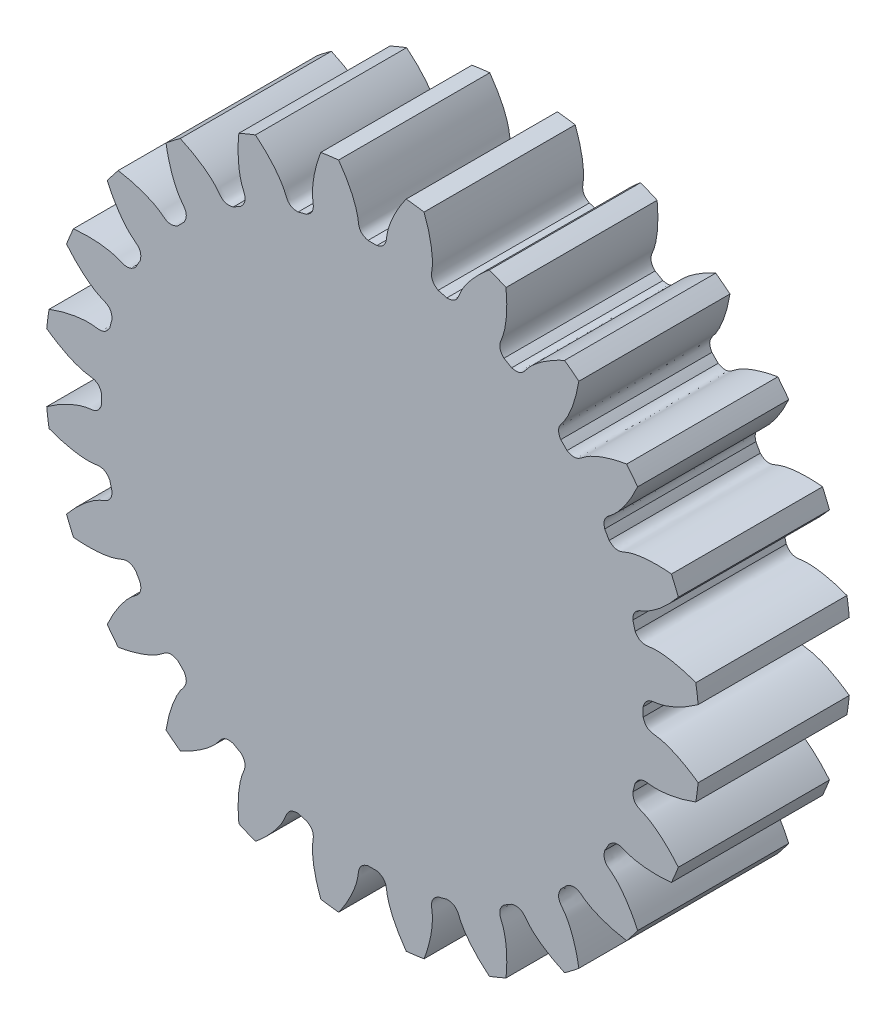
SolidWorks part; units mm, degrees
ref_plane "前视基准面" through (0, 0, 0) normal (0, 0, 1) x (1, 0, 0)
ref_plane "上视基准面" through (0, 0, 0) normal (0, 1, 0) x (1, 0, 0)
ref_plane "右视基准面" through (0, 0, 0) normal (1, 0, 0) x (0, 0, -1)
other "Configuration Table"
sketch "草图1" plane through (0, 0, 0) normal (0, 0, 1) x (1, 0, 0)
  circle A0 centre (0, 0) radius 6.5
extrude "凸台-拉伸1" add sketch "草图1" along normal blind 3
ref_axis "基准轴1" through (0, 0, 3) along (0, 0, -1)
sketch "草图2" plane through (0, 0, 0) normal (0, 0, 1) x (1, 0, 0)
  line L0 (0, 0) -> (0, 6.5) construction
  circle A0 centre (0, 0) radius 6.5 construction
  arc A1 (0.0884, 5.3743) -> (-0.0884, 5.3743) centre (0, 0) ccw
  arc A2 (1.5578, 7.3471) -> (-1.5578, 7.3471) centre (0, 0) ccw
  spline S0 degree 3 poles (0.0884, 5.3743) (0.284, 5.4284) (0.2695, 5.5579) (0.2931, 5.6863) (0.2965, 5.7029) (0.3007, 5.7216) (0.3058, 5.7424) (0.312, 5.7653) (0.3191, 5.7902) (0.3275, 5.8171) (0.3371, 5.846) (0.348, 5.8769) (0.3604, 5.9096) (0.3742, 5.9441) (0.3896, 5.9805) (0.4067, 6.0185) (0.4254, 6.0583) (0.446, 6.0997) (0.4684, 6.1427) (0.4928, 6.1872) (0.5192, 6.2332) (0.5476, 6.2806) (0.5782, 6.3293) (0.611, 6.3792) (0.6461, 6.4304) (0.6834, 6.4827) (0.7232, 6.536) (0.7654, 6.5903) (0.8101, 6.6456) (0.8574, 6.7016) (0.9073, 6.7583) (0.9598, 6.8158) (1.015, 6.8738) (1.0729, 6.9322) (1.1336, 6.9911) (1.1972, 7.0503) (1.2635, 7.1097) (1.3328, 7.1693) (1.4302, 7.2497) (1.506, 7.3084) (1.5578, 7.3471) knots 0 0 0 0 0.143961 0.149818 0.156577 0.164236 0.172796 0.182258 0.19262 0.203884 0.216049 0.229115 0.243082 0.25795 0.273719 0.290389 0.30796 0.326433 0.345806 0.366081 0.387257 0.409333 0.432311 0.45619 0.48097 0.506651 0.533234 0.560717 0.589101 0.618387 0.648574 0.679661 0.71165 0.74454 0.778331 0.813023 0.848616 0.885111 0.922506 1 1 1 1
  spline S1 degree 3 poles (-0.0884, 5.3743) (-0.284, 5.4284) (-0.2695, 5.5579) (-0.2931, 5.6863) (-0.2965, 5.7029) (-0.3007, 5.7216) (-0.3058, 5.7424) (-0.312, 5.7653) (-0.3191, 5.7902) (-0.3275, 5.8171) (-0.3371, 5.846) (-0.348, 5.8769) (-0.3604, 5.9096) (-0.3742, 5.9441) (-0.3896, 5.9805) (-0.4067, 6.0185) (-0.4254, 6.0583) (-0.446, 6.0997) (-0.4684, 6.1427) (-0.4928, 6.1872) (-0.5192, 6.2332) (-0.5476, 6.2806) (-0.5782, 6.3293) (-0.611, 6.3792) (-0.6461, 6.4304) (-0.6834, 6.4827) (-0.7232, 6.536) (-0.7654, 6.5903) (-0.8101, 6.6456) (-0.8574, 6.7016) (-0.9073, 6.7583) (-0.9598, 6.8158) (-1.015, 6.8738) (-1.0729, 6.9322) (-1.1336, 6.9911) (-1.1972, 7.0503) (-1.2635, 7.1097) (-1.3328, 7.1693) (-1.4302, 7.2497) (-1.506, 7.3084) (-1.5578, 7.3471) knots 0 0 0 0 0.143961 0.149818 0.156577 0.164236 0.172796 0.182258 0.19262 0.203884 0.216049 0.229115 0.243082 0.25795 0.273719 0.290389 0.30796 0.326433 0.345806 0.366081 0.387257 0.409333 0.432311 0.45619 0.48097 0.506651 0.533234 0.560717 0.589101 0.618387 0.648574 0.679661 0.71165 0.74454 0.778331 0.813023 0.848616 0.885111 0.922506 1 1 1 1
extrude "切除-拉伸1" cut sketch "草图2" along normal through all
pattern_circular "阵列(圆周)1" count 24 every 15 about axis through (0, 0, 3) along (0, 0, -1) of "切除-拉伸1"
sketch "草图3" plane through (0, 0, 0) normal (0, 0, 1) x (1, 0, 0)
  circle A0 centre (0, 0) radius 6 construction
  dimension "Dn" = 12
